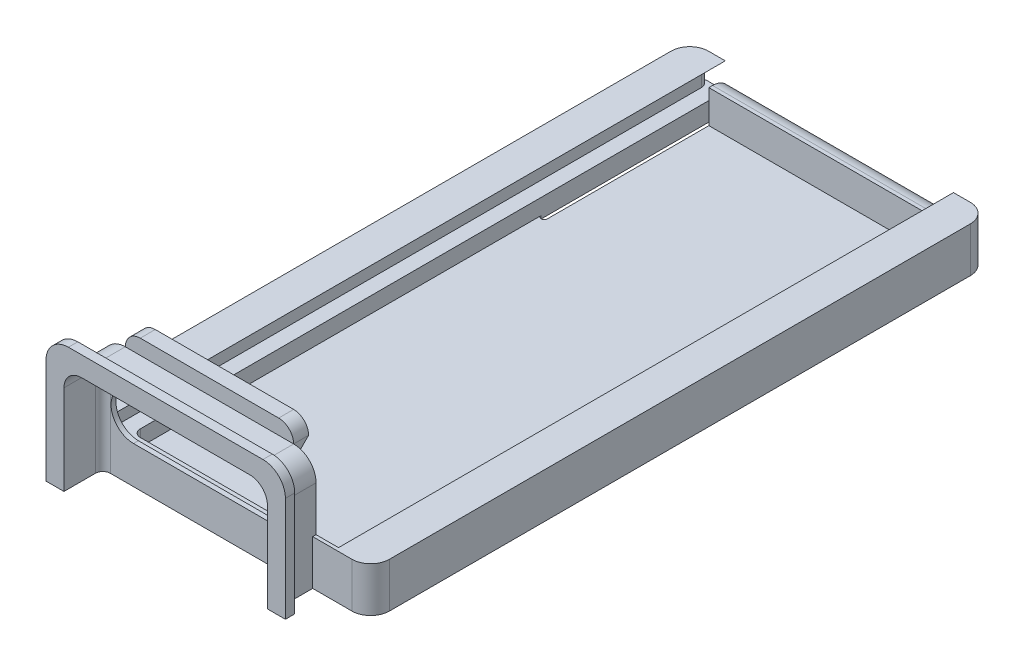
SolidWorks part; units mm, degrees
ref_plane "Front Plane" through (0, 0, 0) normal (0, 0, 1) x (1, 0, 0)
ref_plane "Top Plane" through (0, 0, 0) normal (0, 1, 0) x (1, 0, 0)
ref_plane "Right Plane" through (0, 0, 0) normal (1, 0, 0) x (0, 0, -1)
sketch "Sketch1" plane through (0, 0, 0) normal (0, 0, 1) x (1, 0, 0)
  line L0 (0, 0) -> (14, 0)
  line L5 (-2, 0) -> (0, 0)
  line L6 (-2, 0) -> (-2, 17)
  line L7 (-2, 17) -> (14, 17)
  line L8 (14, 0) -> (14, 17)
  dimension "D1" = 16
  dimension "D2" = 17
  dimension "D3" = 2
extrude "Boss-Extrude1" add sketch "Sketch1" along normal blind 1.25
sketch "Sketch2" plane through (0, 0, 0) normal (0, 0, 1) x (1, 0, 0)
  line L1 (-2, 0) -> (12.25, 0)
  line L2 (-2, 0) -> (-2, 15)
  line L3 (-2, 15) -> (12.25, 15)
  line L4 (12.25, 0) -> (12.25, 15)
  dimension "D1" = 15
  dimension "D2" = 14.25
extrude "Boss-Extrude2" add sketch "Sketch2" against normal blind 4.6
sketch "Sketch3" plane through (0, 0, -4.6) normal (0, 0, -1) x (-1, 0, 0)
  line L2 (2, 16) -> (2, 0)
  line L3 (2, 0) -> (-13.25, 0)
  line L4 (-13.25, 0) -> (-13.25, 16)
  line L5 (-13.25, 16) -> (2, 16)
  line L6 (-13.25, 0) -> (-13.25, 16)
  line L7 (-13.25, 16) -> (2, 16)
  dimension "D1" = 1
fillet "Fillet1" radius 3 2 edges at (12.25, 15, -2.3) (14, 17, 0.625)
sketch "Sketch5" plane through (0, 0, 0) normal (0, 1, 0) x (1, 0, 0)
  line L0 (-2, 4.6) -> (13.25, 4.6) construction
  line L1 (0, 4.6) -> (20, 4.6)
  line L2 (0, 4.6) -> (0, 86.8)
  line L3 (0, 86.8) -> (20, 86.8)
  line L4 (20, 4.6) -> (20, 86.8)
  point P4 (0, 0)
  dimension "D1" = 20
  dimension "D2" = 82.2
extrude "Base Plate" add sketch "Sketch5" along normal blind 6 separate body
sketch "Sketch18" plane through (0, 0, -86.8) normal (0, 0, -1) x (-1, 0, 0)
  line L0 (0, 0.4) -> (-15.25, 0.4)
  line L1 (-17.25, 4.5) -> (-15.25, 6)
  line L2 (-15.25, 0.4) -> (-15.25, 2.5)
  line L3 (-15.25, 2.5) -> (-17.25, 2.5)
  line L4 (-17.25, 2.5) -> (-17.25, 4.5)
  line L5 (-17.25, 4.5) -> (-15.25, 4.5) construction
  line L6 (-15.25, 4.5) -> (-15.25, 6) construction
  line L7 (-20, 6) -> (0, 6) construction
  line L8 (-15.25, 6) -> (0, 6)
  line L9 (-20, 0) -> (0, 0) construction
  line L10 (0, 6) -> (0, 0.4)
  line L11 (0, 6) -> (0, 0) construction
  line L12 (0, 6) -> (-20, 6) construction
  point P2 (0, 0)
  dimension "D1" = 2.1
  dimension "D2" = 2
  dimension "D3" = 2
  dimension "D4" = 2
  dimension "D5" = 0.4
  dimension "D6" = 17.25
extrude "Slot Cut" cut sketch "Sketch18" against normal up to surface (82.2 mm away) up to face at (10, 3, -4.6)
sketch "Sketch8" plane through (0, 0.4, 0) normal (0, 1, 0) x (1, 0, 0)
  line L0 (15.25, 4.6) -> (15.25, 86.8) construction
  line L1 (15.25, 86.8) -> (0, 86.8)
  line L2 (15.25, 86.8) -> (15.25, 83.8)
  line L3 (15.25, 83.8) -> (0, 83.8)
  line L4 (0, 86.8) -> (0, 83.8)
  dimension "D1" = 3
extrude "Rear Tab" add sketch "Sketch8" along normal offset from surface 1.2 and the other way up to next (0.4 mm away) up to face at (17.625, 6, -45.7)
sketch "Sketch22" plane through (0, 0.4, 0) normal (0, 1, 0) x (1, 0, 0)
  line L0 (15.25, 4.6) -> (15.25, 83.8) construction
  line L1 (0, 4.6) -> (15.25, 4.6)
  line L2 (0, 4.6) -> (0, 7.6)
  line L3 (0, 7.6) -> (15.25, 7.6)
  line L4 (15.25, 4.6) -> (15.25, 7.6)
  dimension "D1" = 3
extrude "Front Support Rail" add sketch "Sketch22" along normal up to surface (2.1 mm away) up to face at (16.05, 2.5, -53.32)
sketch "Sketch23" plane through (0, 0, 0) normal (0, 1, 0) x (1, 0, 0)
  line L1 (15.25, 86.8) -> (14.45, 86.8)
  line L2 (15.25, 86.8) -> (15.25, 61.8)
  line L3 (15.25, 61.8) -> (14.45, 61.8)
  line L4 (14.45, 86.8) -> (14.45, 61.8)
  dimension "D1" = 0.8
  dimension "D2" = 25
extrude "Bend Slot" cut sketch "Sketch23" along normal through all
mirror "Mirror1" about plane through (-2, 0, 1.25) normal (1, 0, 0) of bodies 107 101
mirror "Mirror2" about plane through (0, 6, -4.6) normal (1, 0, 0) of bodies 127 117
sketch "Sketch20" plane through (0, 0, -4.6) normal (0, 0, 1) x (1, 0, 0)
  line L0 (-17.25, 4.5) -> (-15.25, 6) construction
  line L1 (20, 6) -> (12.25, 6)
  line L2 (20, 6) -> (20, 0)
  line L3 (20, 0) -> (12.25, 0)
  line L4 (12.25, 6) -> (12.25, 0)
  line L5 (-20, 0) -> (-15.25, 0)
  line L6 (-20, 0) -> (-20, 6)
  line L7 (-20, 6) -> (-15.25, 6)
  line L8 (-15.25, 0) -> (-15.25, 6)
  line L9 (-15.25, 6) -> (-20, 6) construction
  point P10 (0, 0)
  point P11 (0, 0)
  point P15 (0, 0)
  point P16 (-15.25, 6)
extrude "Boss-Extrude3" add sketch "Sketch20" along normal blind 0.45
fillet "Fillet6" radius 2.5 5 edges at (20, 3, -86.8) (0, 4.8, -86.8) (-20, 3, -86.8) (20, 3, -4.15) (-20, 3, -4.15)
sketch "Sketch15" plane through (0, 0, 1.25) normal (0, 0, 1) x (1, 0, 0)
  line L0 (7.5, 8) -> (-11.5, 8) construction
  line L1 (7.5, 5) -> (-11.5, 5)
  line L2 (7.5, 11) -> (-11.5, 11)
  line L3 (-18, 0) -> (14, 0) construction
  line L4 (-2, 8) -> (-2, 0) construction
  line L5 (-18, 0) -> (14, 0) construction
  arc A0 (7.5, 5) -> (7.5, 11) centre (7.5, 8) ccw
  arc A1 (-11.5, 11) -> (-11.5, 5) centre (-11.5, 8) ccw
  point P2 (-2, 8)
  point P7 (0, 0)
  point P13 (-14.5, 8)
  point P14 (10.5, 8)
  point P16 (0, 0)
  point P17 (0, 0)
  point P18 (0, 0)
  point P19 (0, 0)
  point P20 (0, 0)
  dimension "D1" = 6
  dimension "D2" = 8
  dimension "D3" = 25
extrude "Cut-Extrude4" cut sketch "Sketch15" against normal through all
sketch "Sketch16" plane through (0, 0, 1.25) normal (0, 0, 1) x (1, 0, 0)
  line L3 (-15.6, 0) -> (11.6, 0)
  line L6 (11.6, 12) -> (11.6, 0)
  line L7 (-13.25, 14.35) -> (9.25, 14.35)
  line L8 (-15.6, 0) -> (-15.6, 12)
  line L9 (11.6, 12) -> (11.6, 0)
  line L10 (-13.25, 14.35) -> (9.25, 14.35)
  line L11 (-15.6, 0) -> (-15.6, 12)
  arc A4 (11.6, 12) -> (9.25, 14.35) centre (9.25, 12) ccw
  arc A5 (-13.25, 14.35) -> (-15.6, 12) centre (-13.25, 12) ccw
  arc A6 (11.6, 12) -> (9.25, 14.35) centre (9.25, 12) ccw
  arc A7 (-13.25, 14.35) -> (-15.6, 12) centre (-13.25, 12) ccw
  dimension "D1" = 0.65
extrude "Cut-Extrude5" cut sketch "Sketch16" against normal offset from surface (5.2 mm away) 0.65 up to face at (-2, 8, -4.6)
fillet "Fillet5" radius 1 9 edges at (-15.6, 6, -3.95) (-14.9117, 13.6617, -3.95) (-2, 14.35, -3.95) (10.9117, 13.6617, -3.95) (11.6, 6, -3.95) (-15.25, 1.45, -7.6) (15.25, 1.45, -7.6) (-17.25, 3.5, -86.8) (17.25, 3.5, -86.8)
fillet "Fillet7" radius 0.4 4 edges at (-14.45, 0.2, -61.8) (-15.25, 0.2, -61.8) (14.45, 0.2, -61.8) (15.25, 0.2, -61.8)
sketch "Sketch24" plane through (0, 0, -4.6) normal (0, 0, -1) x (-1, 0, 0)
  line L0 (-11, 17) -> (15, 17) construction
  line L1 (-9.25, 15) -> (13.25, 15) construction
  line L2 (-9.25, 15) -> (-9.25, 17)
  line L3 (-9.25, 17) -> (13.25, 17)
  line L4 (13.25, 15) -> (13.25, 17)
  line L7 (-9.25, 15) -> (-9.25, 13)
  line L8 (-9.25, 13) -> (13.25, 13)
  line L9 (13.25, 15) -> (13.25, 13)
extrude "Boss-Extrude4" add sketch "Sketch24" along normal blind 2
chamfer "Chamfer1" distance 2 angle 45 1 edges at (-2, 13, -6.6)
fillet "Fillet8" radius 2 2 edges at (-13.25, 17, -5.6) (9.25, 17, -5.6)
